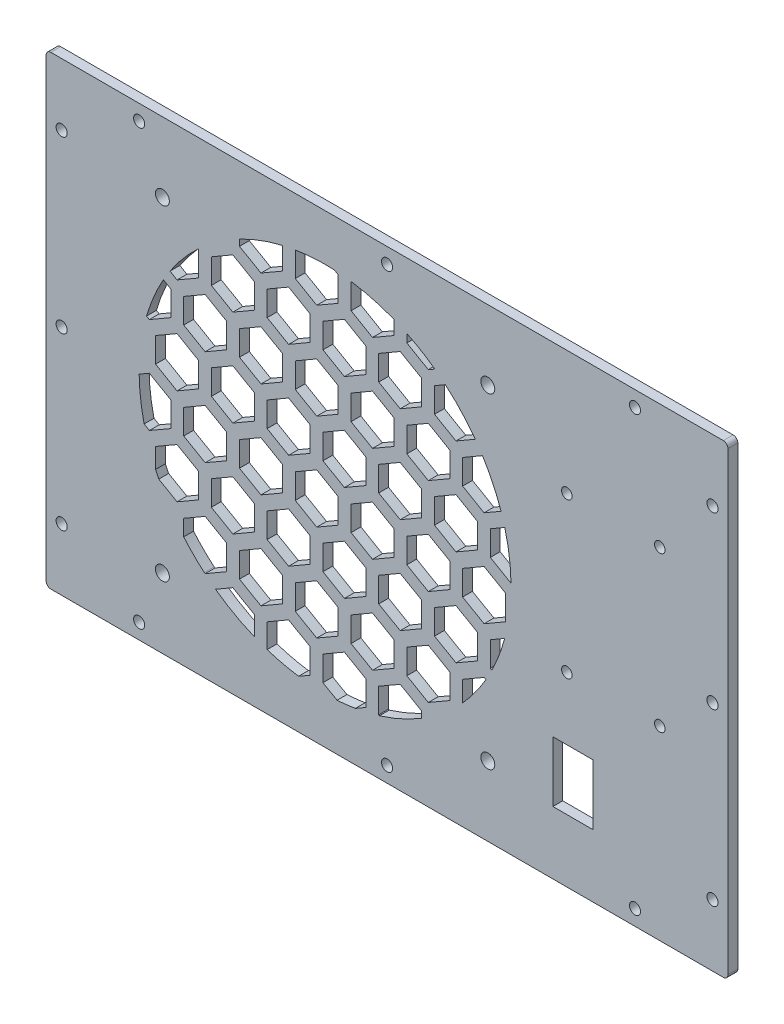
SolidWorks part; units mm, degrees
ref_plane "Front Plane" through (0, 0, 0) normal (0, 0, 1) x (1, 0, 0)
ref_plane "Top Plane" through (0, 0, 0) normal (0, 1, 0) x (1, 0, 0)
ref_plane "Right Plane" through (0, 0, 0) normal (1, 0, 0) x (0, 0, -1)
sketch "Sketch1" plane through (0, 0, 0) normal (0, 0, 1) x (1, 0, 0)
  line L0 (0, 0) -> (0, 75) construction
  line L1 (-110, -75) -> (110, -75)
  line L2 (-110, -75) -> (-110, 75)
  line L3 (-110, 75) -> (110, 75)
  line L4 (110, -75) -> (110, 75)
  line L5 (-110, -75) -> (110, 75) construction
  line L6 (-110, 75) -> (110, -75) construction
  line L15 (0, 0) -> (-110, 0) construction
  point P0 (0, 0)
  dimension "D1" = 220
  dimension "D2" = 150
extrude "Boss-Extrude1" add sketch "Sketch1" along normal blind 3.175 contours L3 L2 L1 L4 region at (0, 0, 0)
hole_wizard "M3 Clearance Hole1" positions "Sketch2" profile "Sketch3" hole size "M3" standard "ANSI Metric" end condition through all
sketch "Sketch2" plane through (0, 0, 3.175) normal (0, 0, 1) x (1, 0, 0)
  line L1 (-105, -70) -> (105, -70)
  line L2 (-105, -70) -> (-105, 70)
  line L3 (-105, 70) -> (105, 70)
  line L4 (105, -70) -> (105, 70)
  line L5 (-105, -70) -> (105, 70) construction
  line L6 (-105, 70) -> (105, -70) construction
  line L7 (-110, -75) -> (-110, 75) construction
  line L8 (-110, 75) -> (110, 75) construction
  point P2 (0, 0)
  point P113 (-80, 70)
  point P115 (80, 70)
  point P116 (0, 70)
  point P118 (-105, 55)
  point P120 (-105, 0)
  point P122 (-105, -55)
  point P124 (-80, -70)
  point P126 (0, -70)
  point P128 (80, -70)
  point P130 (105, -55)
  point P132 (105, 0)
  point P134 (105, 55)
  dimension "D1" = 5
  dimension "D2" = 5
  dimension "D3" = 80
  dimension "D4" = 80
  dimension "D5" = 55
  dimension "D6" = 55
sketch "Sketch3" plane through (0, 0, 3.175) normal (1, 0, 0) x (0, -1, 0)
  line L0 (0, 0) -> (0, 3.175)
  line L1 (0, 3.175) -> (1.8, 3.175)
  line L2 (1.8, 3.175) -> (1.8, 0)
  line L5 (1.8, 0) -> (0, 0)
  line L11 (0, -6.35) -> (0, 107.95) construction
  dimension "Thru Hole Dia." = 3.6
  dimension "Thru Hole Depth" = 3.175
sketch "Sketch4" plane through (0, 0, 3.175) normal (0, 0, 1) x (1, 0, 0)
  line L1 (-5, -5) -> (5, -5)
  line L2 (-5, -5) -> (-5, 5)
  line L3 (-5, 5) -> (5, 5)
  line L4 (5, -5) -> (5, 5)
  line L5 (-5, -5) -> (5, 5) construction
  line L6 (-5, 5) -> (5, -5) construction
  point P0 (0, 0)
  dimension "D1" = 10
  dimension "D2" = 10
extrude "Boss-Extrude2" add sketch "Sketch4" against normal through all
fillet "Fillet2" radius 1.5 4 edges at (-110, -75, 1.5875) (110, -75, 1.5875) (110, 75, 1.5875) (-110, 75, 1.5875)
sketch "Sketch6" plane through (0, 0, 3.175) normal (0, 0, 1) x (1, 0, 0)
  line L0 (-108.5, -75) -> (108.5, -75) construction
  line L1 (-80, -60) -> (40, -60)
  line L2 (-80, -60) -> (-80, 60)
  line L3 (-80, 60) -> (40, 60)
  line L4 (40, -60) -> (40, 60)
  line L5 (-80, -60) -> (40, 60) construction
  line L6 (-80, 60) -> (40, -60) construction
  line L13 (-110, -73.5) -> (-110, 73.5) construction
  line L17 (-72.5, -52.5) -> (32.5, -52.5)
  line L18 (-72.5, -52.5) -> (-72.5, 52.5)
  line L19 (-72.5, 52.5) -> (32.5, 52.5)
  line L20 (32.5, -52.5) -> (32.5, 52.5)
  line L21 (-72.5, -52.5) -> (32.5, 52.5) construction
  line L22 (-72.5, 52.5) -> (32.5, -52.5) construction
  circle A0 centre (-20, 0) radius 60
  point P0 (-20, 0)
  point P5 (-20, 0)
  point P6 (-20, 0)
  dimension "D7" = 120
  dimension "D1" = 120
  dimension "D2" = 120
  dimension "D3" = 15
  dimension "D4" = 30
  dimension "D5" = 105
  dimension "D6" = 105
hole_wizard "M4 Clearance Hole1" positions "Sketch7" profile "Sketch9" hole size "M4" standard "ANSI Metric" end condition through all
sketch "Sketch7" plane through (0, 0, 3.175) normal (0, 0, 1) x (1, 0, 0)
  point P0 (-72.5, 52.5)
  point P3 (32.5, 52.5)
  point P6 (32.5, -52.5)
  point P9 (-72.5, -52.5)
sketch "Sketch9" plane through (-72.5, 52.5, 3.175) normal (1, 0, 0) x (0, -1, 0)
  line L0 (0, 0) -> (0, 3.175)
  line L1 (0, 3.175) -> (2.25, 3.175)
  line L2 (2.25, 3.175) -> (2.25, 0)
  line L5 (2.25, 0) -> (0, 0)
  line L11 (0, -6.35) -> (0, 107.95) construction
  dimension "Thru Hole Dia." = 4.5
  dimension "Thru Hole Depth" = 3.175
extrude "Cut-Extrude1" cut sketch "Sketch6" against normal blind 10 contours L20 A0 L19 L18 L17 | L18 A0 | L19 A0 | A0 L20 | L17 A0 region at (-20, -55.5167, 3.175) region at (-75.5167, 0, 3.175) region at (-20, 0, 3.175) region at (35.5167, 0, 3.175) region at (-20, 55.5167, 3.175)
sketch "Sketch11" plane through (0, 0, 3.175) normal (0, 0, 1) x (1, 0, 0)
  line L0 (-58.6995, -29.7786) -> (-65.6277, -33.7786)
  line L1 (-76.6995, -29.7786) -> (-83.6277, -33.7786)
  line L2 (-83.6277, -33.7786) -> (-83.6277, -41.7786)
  line L3 (-83.6277, -41.7786) -> (-76.6995, -45.7786)
  line L4 (-76.6995, -45.7786) -> (-69.7713, -41.7786)
  line L5 (-69.7713, -41.7786) -> (-69.7713, -33.7786)
  line L6 (-69.7713, -33.7786) -> (-76.6995, -29.7786)
  line L13 (-67.7713, -45.2427) -> (-74.6995, -49.2427)
  line L14 (-74.6995, -49.2427) -> (-74.6995, -57.2427)
  line L15 (-74.6995, -57.2427) -> (-67.7713, -61.2427)
  line L16 (-67.7713, -61.2427) -> (-60.8431, -57.2427)
  line L17 (-60.8431, -57.2427) -> (-60.8431, -49.2427)
  line L18 (-60.8431, -49.2427) -> (-67.7713, -45.2427)
  line L19 (-65.6277, -33.7786) -> (-65.6277, -41.7786)
  line L20 (-65.6277, -41.7786) -> (-58.6995, -45.7786)
  line L21 (-58.6995, -45.7786) -> (-51.7713, -41.7786)
  line L22 (-51.7713, -41.7786) -> (-51.7713, -33.7786)
  line L23 (-51.7713, -33.7786) -> (-58.6995, -29.7786)
  line L24 (-49.7713, -45.2427) -> (-56.6995, -49.2427)
  line L25 (-56.6995, -49.2427) -> (-56.6995, -57.2427)
  line L26 (-56.6995, -57.2427) -> (-49.7713, -61.2427)
  line L27 (-49.7713, -61.2427) -> (-42.8431, -57.2427)
  line L28 (-42.8431, -57.2427) -> (-42.8431, -49.2427)
  line L29 (-42.8431, -49.2427) -> (-49.7713, -45.2427)
  line L30 (-40.6995, -29.7786) -> (-47.6277, -33.7786)
  line L31 (-47.6277, -33.7786) -> (-47.6277, -41.7786)
  line L32 (-47.6277, -41.7786) -> (-40.6995, -45.7786)
  line L33 (-40.6995, -45.7786) -> (-33.7713, -41.7786)
  line L34 (-33.7713, -41.7786) -> (-33.7713, -33.7786)
  line L35 (-33.7713, -33.7786) -> (-40.6995, -29.7786)
  line L36 (-31.7713, -45.2427) -> (-38.6995, -49.2427)
  line L37 (-38.6995, -49.2427) -> (-38.6995, -57.2427)
  line L38 (-38.6995, -57.2427) -> (-31.7713, -61.2427)
  line L39 (-31.7713, -61.2427) -> (-24.8431, -57.2427)
  line L40 (-24.8431, -57.2427) -> (-24.8431, -49.2427)
  line L41 (-24.8431, -49.2427) -> (-31.7713, -45.2427)
  line L42 (-22.6995, -29.7786) -> (-29.6277, -33.7786)
  line L43 (-29.6277, -33.7786) -> (-29.6277, -41.7786)
  line L44 (-29.6277, -41.7786) -> (-22.6995, -45.7786)
  line L45 (-22.6995, -45.7786) -> (-15.7713, -41.7786)
  line L46 (-15.7713, -41.7786) -> (-15.7713, -33.7786)
  line L47 (-15.7713, -33.7786) -> (-22.6995, -29.7786)
  line L48 (-13.7713, -45.2427) -> (-20.6995, -49.2427)
  line L49 (-20.6995, -49.2427) -> (-20.6995, -57.2427)
  line L50 (-20.6995, -57.2427) -> (-13.7713, -61.2427)
  line L51 (-13.7713, -61.2427) -> (-6.8431, -57.2427)
  line L52 (-6.8431, -57.2427) -> (-6.8431, -49.2427)
  line L53 (-6.8431, -49.2427) -> (-13.7713, -45.2427)
  line L54 (-4.6995, -29.7786) -> (-11.6277, -33.7786)
  line L55 (-11.6277, -33.7786) -> (-11.6277, -41.7786)
  line L56 (-11.6277, -41.7786) -> (-4.6995, -45.7786)
  line L57 (-4.6995, -45.7786) -> (2.2287, -41.7786)
  line L58 (2.2287, -41.7786) -> (2.2287, -33.7786)
  line L59 (2.2287, -33.7786) -> (-4.6995, -29.7786)
  line L60 (4.2287, -45.2427) -> (-2.6995, -49.2427)
  line L61 (-2.6995, -49.2427) -> (-2.6995, -57.2427)
  line L62 (-2.6995, -57.2427) -> (4.2287, -61.2427)
  line L63 (4.2287, -61.2427) -> (11.1569, -57.2427)
  line L64 (11.1569, -57.2427) -> (11.1569, -49.2427)
  line L65 (11.1569, -49.2427) -> (4.2287, -45.2427)
  line L66 (13.3005, -29.7786) -> (6.3723, -33.7786)
  line L67 (6.3723, -33.7786) -> (6.3723, -41.7786)
  line L68 (6.3723, -41.7786) -> (13.3005, -45.7786)
  line L69 (13.3005, -45.7786) -> (20.2287, -41.7786)
  line L70 (20.2287, -41.7786) -> (20.2287, -33.7786)
  line L71 (20.2287, -33.7786) -> (13.3005, -29.7786)
  line L72 (22.2287, -45.2427) -> (15.3005, -49.2427)
  line L73 (15.3005, -49.2427) -> (15.3005, -57.2427)
  line L74 (15.3005, -57.2427) -> (22.2287, -61.2427)
  line L75 (22.2287, -61.2427) -> (29.1569, -57.2427)
  line L76 (29.1569, -57.2427) -> (29.1569, -49.2427)
  line L77 (29.1569, -49.2427) -> (22.2287, -45.2427)
  line L78 (31.3005, -29.7786) -> (24.3723, -33.7786)
  line L79 (24.3723, -33.7786) -> (24.3723, -41.7786)
  line L80 (24.3723, -41.7786) -> (31.3005, -45.7786)
  line L81 (31.3005, -45.7786) -> (38.2287, -41.7786)
  line L82 (38.2287, -41.7786) -> (38.2287, -33.7786)
  line L83 (38.2287, -33.7786) -> (31.3005, -29.7786)
  line L84 (40.2287, -45.2427) -> (33.3005, -49.2427)
  line L85 (33.3005, -49.2427) -> (33.3005, -57.2427)
  line L86 (33.3005, -57.2427) -> (40.2287, -61.2427)
  line L87 (40.2287, -61.2427) -> (47.1569, -57.2427)
  line L88 (47.1569, -57.2427) -> (47.1569, -49.2427)
  line L89 (47.1569, -49.2427) -> (40.2287, -45.2427)
  line L90 (-58.6995, 1.2214) -> (-65.6277, -2.7786)
  line L91 (-65.6277, -2.7786) -> (-65.6277, -10.7786)
  line L92 (-65.6277, -10.7786) -> (-58.6995, -14.7786)
  line L93 (-58.6995, -14.7786) -> (-51.7713, -10.7786)
  line L94 (-51.7713, -10.7786) -> (-51.7713, -2.7786)
  line L95 (-51.7713, -2.7786) -> (-58.6995, 1.2214)
  line L96 (-49.7713, -14.2427) -> (-56.6995, -18.2427)
  line L97 (-56.6995, -18.2427) -> (-56.6995, -26.2427)
  line L98 (-56.6995, -26.2427) -> (-49.7713, -30.2427)
  line L99 (-49.7713, -30.2427) -> (-42.8431, -26.2427)
  line L100 (-42.8431, -26.2427) -> (-42.8431, -18.2427)
  line L101 (-42.8431, -18.2427) -> (-49.7713, -14.2427)
  line L102 (-40.6995, 1.2214) -> (-47.6277, -2.7786)
  line L103 (-47.6277, -2.7786) -> (-47.6277, -10.7786)
  line L104 (-47.6277, -10.7786) -> (-40.6995, -14.7786)
  line L105 (-40.6995, -14.7786) -> (-33.7713, -10.7786)
  line L106 (-33.7713, -10.7786) -> (-33.7713, -2.7786)
  line L107 (-33.7713, -2.7786) -> (-40.6995, 1.2214)
  line L108 (-31.7713, -14.2427) -> (-38.6995, -18.2427)
  line L109 (-38.6995, -18.2427) -> (-38.6995, -26.2427)
  line L110 (-38.6995, -26.2427) -> (-31.7713, -30.2427)
  line L111 (-31.7713, -30.2427) -> (-24.8431, -26.2427)
  line L112 (-24.8431, -26.2427) -> (-24.8431, -18.2427)
  line L113 (-24.8431, -18.2427) -> (-31.7713, -14.2427)
  line L114 (-22.6995, 1.2214) -> (-29.6277, -2.7786)
  line L115 (-29.6277, -2.7786) -> (-29.6277, -10.7786)
  line L116 (-29.6277, -10.7786) -> (-22.6995, -14.7786)
  line L117 (-22.6995, -14.7786) -> (-15.7713, -10.7786)
  line L118 (-15.7713, -10.7786) -> (-15.7713, -2.7786)
  line L119 (-15.7713, -2.7786) -> (-22.6995, 1.2214)
  line L120 (-13.7713, -14.2427) -> (-20.6995, -18.2427)
  line L121 (-20.6995, -18.2427) -> (-20.6995, -26.2427)
  line L122 (-20.6995, -26.2427) -> (-13.7713, -30.2427)
  line L123 (-13.7713, -30.2427) -> (-6.8431, -26.2427)
  line L124 (-6.8431, -26.2427) -> (-6.8431, -18.2427)
  line L125 (-6.8431, -18.2427) -> (-13.7713, -14.2427)
  line L126 (-4.6995, 1.2214) -> (-11.6277, -2.7786)
  line L127 (-11.6277, -2.7786) -> (-11.6277, -10.7786)
  line L128 (-11.6277, -10.7786) -> (-4.6995, -14.7786)
  line L129 (-4.6995, -14.7786) -> (2.2287, -10.7786)
  line L130 (2.2287, -10.7786) -> (2.2287, -2.7786)
  line L131 (2.2287, -2.7786) -> (-4.6995, 1.2214)
  line L132 (4.2287, -14.2427) -> (-2.6995, -18.2427)
  line L133 (-2.6995, -18.2427) -> (-2.6995, -26.2427)
  line L134 (-2.6995, -26.2427) -> (4.2287, -30.2427)
  line L135 (4.2287, -30.2427) -> (11.1569, -26.2427)
  line L136 (11.1569, -26.2427) -> (11.1569, -18.2427)
  line L137 (11.1569, -18.2427) -> (4.2287, -14.2427)
  line L138 (13.3005, 1.2214) -> (6.3723, -2.7786)
  line L139 (6.3723, -2.7786) -> (6.3723, -10.7786)
  line L140 (6.3723, -10.7786) -> (13.3005, -14.7786)
  line L141 (13.3005, -14.7786) -> (20.2287, -10.7786)
  line L142 (20.2287, -10.7786) -> (20.2287, -2.7786)
  line L143 (20.2287, -2.7786) -> (13.3005, 1.2214)
  line L144 (22.2287, -14.2427) -> (15.3005, -18.2427)
  line L145 (15.3005, -18.2427) -> (15.3005, -26.2427)
  line L146 (15.3005, -26.2427) -> (22.2287, -30.2427)
  line L147 (22.2287, -30.2427) -> (29.1569, -26.2427)
  line L148 (29.1569, -26.2427) -> (29.1569, -18.2427)
  line L149 (29.1569, -18.2427) -> (22.2287, -14.2427)
  line L150 (31.3005, 1.2214) -> (24.3723, -2.7786)
  line L151 (24.3723, -2.7786) -> (24.3723, -10.7786)
  line L152 (24.3723, -10.7786) -> (31.3005, -14.7786)
  line L153 (31.3005, -14.7786) -> (38.2287, -10.7786)
  line L154 (38.2287, -10.7786) -> (38.2287, -2.7786)
  line L155 (38.2287, -2.7786) -> (31.3005, 1.2214)
  line L156 (40.2287, -14.2427) -> (33.3005, -18.2427)
  line L157 (33.3005, -18.2427) -> (33.3005, -26.2427)
  line L158 (33.3005, -26.2427) -> (40.2287, -30.2427)
  line L159 (40.2287, -30.2427) -> (47.1569, -26.2427)
  line L160 (47.1569, -26.2427) -> (47.1569, -18.2427)
  line L161 (47.1569, -18.2427) -> (40.2287, -14.2427)
  line L162 (-58.6995, 32.2214) -> (-65.6277, 28.2214)
  line L163 (-65.6277, 28.2214) -> (-65.6277, 20.2214)
  line L164 (-65.6277, 20.2214) -> (-58.6995, 16.2214)
  line L165 (-58.6995, 16.2214) -> (-51.7713, 20.2214)
  line L166 (-51.7713, 20.2214) -> (-51.7713, 28.2214)
  line L167 (-51.7713, 28.2214) -> (-58.6995, 32.2214)
  line L168 (-49.7713, 16.7573) -> (-56.6995, 12.7573)
  line L169 (-56.6995, 12.7573) -> (-56.6995, 4.7573)
  line L170 (-56.6995, 4.7573) -> (-49.7713, 0.7573)
  line L171 (-49.7713, 0.7573) -> (-42.8431, 4.7573)
  line L172 (-42.8431, 4.7573) -> (-42.8431, 12.7573)
  line L173 (-42.8431, 12.7573) -> (-49.7713, 16.7573)
  line L174 (-40.6995, 32.2214) -> (-47.6277, 28.2214)
  line L175 (-47.6277, 28.2214) -> (-47.6277, 20.2214)
  line L176 (-47.6277, 20.2214) -> (-40.6995, 16.2214)
  line L177 (-40.6995, 16.2214) -> (-33.7713, 20.2214)
  line L178 (-33.7713, 20.2214) -> (-33.7713, 28.2214)
  line L179 (-33.7713, 28.2214) -> (-40.6995, 32.2214)
  line L180 (-31.7713, 16.7573) -> (-38.6995, 12.7573)
  line L181 (-38.6995, 12.7573) -> (-38.6995, 4.7573)
  line L182 (-38.6995, 4.7573) -> (-31.7713, 0.7573)
  line L183 (-31.7713, 0.7573) -> (-24.8431, 4.7573)
  line L184 (-24.8431, 4.7573) -> (-24.8431, 12.7573)
  line L185 (-24.8431, 12.7573) -> (-31.7713, 16.7573)
  line L186 (-22.6995, 32.2214) -> (-29.6277, 28.2214)
  line L187 (-29.6277, 28.2214) -> (-29.6277, 20.2214)
  line L188 (-29.6277, 20.2214) -> (-22.6995, 16.2214)
  line L189 (-22.6995, 16.2214) -> (-15.7713, 20.2214)
  line L190 (-15.7713, 20.2214) -> (-15.7713, 28.2214)
  line L191 (-15.7713, 28.2214) -> (-22.6995, 32.2214)
  line L192 (-13.7713, 16.7573) -> (-20.6995, 12.7573)
  line L193 (-20.6995, 12.7573) -> (-20.6995, 4.7573)
  line L194 (-20.6995, 4.7573) -> (-13.7713, 0.7573)
  line L195 (-13.7713, 0.7573) -> (-6.8431, 4.7573)
  line L196 (-6.8431, 4.7573) -> (-6.8431, 12.7573)
  line L197 (-6.8431, 12.7573) -> (-13.7713, 16.7573)
  line L198 (-4.6995, 32.2214) -> (-11.6277, 28.2214)
  line L199 (-11.6277, 28.2214) -> (-11.6277, 20.2214)
  line L200 (-11.6277, 20.2214) -> (-4.6995, 16.2214)
  line L201 (-4.6995, 16.2214) -> (2.2287, 20.2214)
  line L202 (2.2287, 20.2214) -> (2.2287, 28.2214)
  line L203 (2.2287, 28.2214) -> (-4.6995, 32.2214)
  line L204 (4.2287, 16.7573) -> (-2.6995, 12.7573)
  line L205 (-2.6995, 12.7573) -> (-2.6995, 4.7573)
  line L206 (-2.6995, 4.7573) -> (4.2287, 0.7573)
  line L207 (4.2287, 0.7573) -> (11.1569, 4.7573)
  line L208 (11.1569, 4.7573) -> (11.1569, 12.7573)
  line L209 (11.1569, 12.7573) -> (4.2287, 16.7573)
  line L210 (13.3005, 32.2214) -> (6.3723, 28.2214)
  line L211 (6.3723, 28.2214) -> (6.3723, 20.2214)
  line L212 (6.3723, 20.2214) -> (13.3005, 16.2214)
  line L213 (13.3005, 16.2214) -> (20.2287, 20.2214)
  line L214 (20.2287, 20.2214) -> (20.2287, 28.2214)
  line L215 (20.2287, 28.2214) -> (13.3005, 32.2214)
  line L216 (22.2287, 16.7573) -> (15.3005, 12.7573)
  line L217 (15.3005, 12.7573) -> (15.3005, 4.7573)
  line L218 (15.3005, 4.7573) -> (22.2287, 0.7573)
  line L219 (22.2287, 0.7573) -> (29.1569, 4.7573)
  line L220 (29.1569, 4.7573) -> (29.1569, 12.7573)
  line L221 (29.1569, 12.7573) -> (22.2287, 16.7573)
  line L222 (31.3005, 32.2214) -> (24.3723, 28.2214)
  line L223 (24.3723, 28.2214) -> (24.3723, 20.2214)
  line L224 (24.3723, 20.2214) -> (31.3005, 16.2214)
  line L225 (31.3005, 16.2214) -> (38.2287, 20.2214)
  line L226 (38.2287, 20.2214) -> (38.2287, 28.2214)
  line L227 (38.2287, 28.2214) -> (31.3005, 32.2214)
  line L228 (40.2287, 16.7573) -> (33.3005, 12.7573)
  line L229 (33.3005, 12.7573) -> (33.3005, 4.7573)
  line L230 (33.3005, 4.7573) -> (40.2287, 0.7573)
  line L231 (40.2287, 0.7573) -> (47.1569, 4.7573)
  line L232 (47.1569, 4.7573) -> (47.1569, 12.7573)
  line L233 (47.1569, 12.7573) -> (40.2287, 16.7573)
  line L234 (-58.6995, 63.2214) -> (-65.6277, 59.2214)
  line L235 (-65.6277, 59.2214) -> (-65.6277, 51.2214)
  line L236 (-65.6277, 51.2214) -> (-58.6995, 47.2214)
  line L237 (-58.6995, 47.2214) -> (-51.7713, 51.2214)
  line L238 (-51.7713, 51.2214) -> (-51.7713, 59.2214)
  line L239 (-51.7713, 59.2214) -> (-58.6995, 63.2214)
  line L240 (-49.7713, 47.7573) -> (-56.6995, 43.7573)
  line L241 (-56.6995, 43.7573) -> (-56.6995, 35.7573)
  line L242 (-56.6995, 35.7573) -> (-49.7713, 31.7573)
  line L243 (-49.7713, 31.7573) -> (-42.8431, 35.7573)
  line L244 (-42.8431, 35.7573) -> (-42.8431, 43.7573)
  line L245 (-42.8431, 43.7573) -> (-49.7713, 47.7573)
  line L246 (-40.6995, 63.2214) -> (-47.6277, 59.2214)
  line L247 (-47.6277, 59.2214) -> (-47.6277, 51.2214)
  line L248 (-47.6277, 51.2214) -> (-40.6995, 47.2214)
  line L249 (-40.6995, 47.2214) -> (-33.7713, 51.2214)
  line L250 (-33.7713, 51.2214) -> (-33.7713, 59.2214)
  line L251 (-33.7713, 59.2214) -> (-40.6995, 63.2214)
  line L252 (-31.7713, 47.7573) -> (-38.6995, 43.7573)
  line L253 (-38.6995, 43.7573) -> (-38.6995, 35.7573)
  line L254 (-38.6995, 35.7573) -> (-31.7713, 31.7573)
  line L255 (-31.7713, 31.7573) -> (-24.8431, 35.7573)
  line L256 (-24.8431, 35.7573) -> (-24.8431, 43.7573)
  line L257 (-24.8431, 43.7573) -> (-31.7713, 47.7573)
  line L258 (-22.6995, 63.2214) -> (-29.6277, 59.2214)
  line L259 (-29.6277, 59.2214) -> (-29.6277, 51.2214)
  line L260 (-29.6277, 51.2214) -> (-22.6995, 47.2214)
  line L261 (-22.6995, 47.2214) -> (-15.7713, 51.2214)
  line L262 (-15.7713, 51.2214) -> (-15.7713, 59.2214)
  line L263 (-15.7713, 59.2214) -> (-22.6995, 63.2214)
  line L264 (-13.7713, 47.7573) -> (-20.6995, 43.7573)
  line L265 (-20.6995, 43.7573) -> (-20.6995, 35.7573)
  line L266 (-20.6995, 35.7573) -> (-13.7713, 31.7573)
  line L267 (-13.7713, 31.7573) -> (-6.8431, 35.7573)
  line L268 (-6.8431, 35.7573) -> (-6.8431, 43.7573)
  line L269 (-6.8431, 43.7573) -> (-13.7713, 47.7573)
  line L270 (-4.6995, 63.2214) -> (-11.6277, 59.2214)
  line L271 (-11.6277, 59.2214) -> (-11.6277, 51.2214)
  line L272 (-11.6277, 51.2214) -> (-4.6995, 47.2214)
  line L273 (-4.6995, 47.2214) -> (2.2287, 51.2214)
  line L274 (2.2287, 51.2214) -> (2.2287, 59.2214)
  line L275 (2.2287, 59.2214) -> (-4.6995, 63.2214)
  line L276 (4.2287, 47.7573) -> (-2.6995, 43.7573)
  line L277 (-2.6995, 43.7573) -> (-2.6995, 35.7573)
  line L278 (-2.6995, 35.7573) -> (4.2287, 31.7573)
  line L279 (4.2287, 31.7573) -> (11.1569, 35.7573)
  line L280 (11.1569, 35.7573) -> (11.1569, 43.7573)
  line L281 (11.1569, 43.7573) -> (4.2287, 47.7573)
  line L282 (13.3005, 63.2214) -> (6.3723, 59.2214)
  line L283 (6.3723, 59.2214) -> (6.3723, 51.2214)
  line L284 (6.3723, 51.2214) -> (13.3005, 47.2214)
  line L285 (13.3005, 47.2214) -> (20.2287, 51.2214)
  line L286 (20.2287, 51.2214) -> (20.2287, 59.2214)
  line L287 (20.2287, 59.2214) -> (13.3005, 63.2214)
  line L288 (22.2287, 47.7573) -> (15.3005, 43.7573)
  line L289 (15.3005, 43.7573) -> (15.3005, 35.7573)
  line L290 (15.3005, 35.7573) -> (22.2287, 31.7573)
  line L291 (22.2287, 31.7573) -> (29.1569, 35.7573)
  line L292 (29.1569, 35.7573) -> (29.1569, 43.7573)
  line L293 (29.1569, 43.7573) -> (22.2287, 47.7573)
  line L294 (31.3005, 63.2214) -> (24.3723, 59.2214)
  line L295 (24.3723, 59.2214) -> (24.3723, 51.2214)
  line L296 (24.3723, 51.2214) -> (31.3005, 47.2214)
  line L297 (31.3005, 47.2214) -> (38.2287, 51.2214)
  line L298 (38.2287, 51.2214) -> (38.2287, 59.2214)
  line L299 (38.2287, 59.2214) -> (31.3005, 63.2214)
  line L300 (40.2287, 47.7573) -> (33.3005, 43.7573)
  line L301 (33.3005, 43.7573) -> (33.3005, 35.7573)
  line L302 (33.3005, 35.7573) -> (40.2287, 31.7573)
  line L303 (40.2287, 31.7573) -> (47.1569, 35.7573)
  line L304 (47.1569, 35.7573) -> (47.1569, 43.7573)
  line L305 (47.1569, 43.7573) -> (40.2287, 47.7573)
  line L306 (-76.6995, 1.2214) -> (-83.6277, -2.7786)
  line L307 (-83.6277, -2.7786) -> (-83.6277, -10.7786)
  line L308 (-83.6277, -10.7786) -> (-76.6995, -14.7786)
  line L309 (-76.6995, -14.7786) -> (-69.7713, -10.7786)
  line L310 (-69.7713, -10.7786) -> (-69.7713, -2.7786)
  line L311 (-69.7713, -2.7786) -> (-76.6995, 1.2214)
  line L312 (-67.7713, -14.2427) -> (-74.6995, -18.2427)
  line L313 (-74.6995, -18.2427) -> (-74.6995, -26.2427)
  line L314 (-74.6995, -26.2427) -> (-67.7713, -30.2427)
  line L315 (-67.7713, -30.2427) -> (-60.8431, -26.2427)
  line L316 (-60.8431, -26.2427) -> (-60.8431, -18.2427)
  line L317 (-60.8431, -18.2427) -> (-67.7713, -14.2427)
  line L318 (-76.6995, 32.2214) -> (-83.6277, 28.2214)
  line L319 (-83.6277, 28.2214) -> (-83.6277, 20.2214)
  line L320 (-83.6277, 20.2214) -> (-76.6995, 16.2214)
  line L321 (-76.6995, 16.2214) -> (-69.7713, 20.2214)
  line L322 (-69.7713, 20.2214) -> (-69.7713, 28.2214)
  line L323 (-69.7713, 28.2214) -> (-76.6995, 32.2214)
  line L324 (-67.7713, 16.7573) -> (-74.6995, 12.7573)
  line L325 (-74.6995, 12.7573) -> (-74.6995, 4.7573)
  line L326 (-74.6995, 4.7573) -> (-67.7713, 0.7573)
  line L327 (-67.7713, 0.7573) -> (-60.8431, 4.7573)
  line L328 (-60.8431, 4.7573) -> (-60.8431, 12.7573)
  line L329 (-60.8431, 12.7573) -> (-67.7713, 16.7573)
  line L330 (-76.6995, 63.2214) -> (-83.6277, 59.2214)
  line L331 (-83.6277, 59.2214) -> (-83.6277, 51.2214)
  line L332 (-83.6277, 51.2214) -> (-76.6995, 47.2214)
  line L333 (-76.6995, 47.2214) -> (-69.7713, 51.2214)
  line L334 (-69.7713, 51.2214) -> (-69.7713, 59.2214)
  line L335 (-69.7713, 59.2214) -> (-76.6995, 63.2214)
  line L336 (-67.7713, 47.7573) -> (-74.6995, 43.7573)
  line L337 (-74.6995, 43.7573) -> (-74.6995, 35.7573)
  line L338 (-74.6995, 35.7573) -> (-67.7713, 31.7573)
  line L339 (-67.7713, 31.7573) -> (-60.8431, 35.7573)
  line L340 (-60.8431, 35.7573) -> (-60.8431, 43.7573)
  line L341 (-60.8431, 43.7573) -> (-67.7713, 47.7573)
  line L346 (-110, 73.5) -> (-110, -73.5)
  line L347 (-108.5, -75) -> (108.5, -75)
  line L348 (110, -73.5) -> (110, 73.5)
  line L349 (108.5, 75) -> (-108.5, 75)
  line L350 (-110, 73.5) -> (-110, -73.5)
  line L351 (-108.5, -75) -> (108.5, -75)
  line L352 (110, -73.5) -> (110, 73.5)
  line L353 (108.5, 75) -> (-108.5, 75)
  circle A0 centre (-76.6995, -37.7786) radius 6.9282 construction
  circle A2 centre (-67.7713, -53.2427) radius 6.9282 construction
  arc A7 (-110, -73.5) -> (-108.5, -75) centre (-108.5, -73.5) ccw
  arc A8 (108.5, -75) -> (110, -73.5) centre (108.5, -73.5) ccw
  arc A9 (110, 73.5) -> (108.5, 75) centre (108.5, 73.5) ccw
  arc A10 (-108.5, 75) -> (-110, 73.5) centre (-108.5, 73.5) ccw
  arc A11 (-110, -73.5) -> (-108.5, -75) centre (-108.5, -73.5) ccw
  arc A12 (108.5, -75) -> (110, -73.5) centre (108.5, -73.5) ccw
  arc A13 (110, 73.5) -> (108.5, 75) centre (108.5, 73.5) ccw
  arc A14 (-108.5, 75) -> (-110, 73.5) centre (-108.5, 73.5) ccw
  circle M347 centre (-20, 0) radius 60
  dimension "D1" = 8
  dimension "D2" = 4
  dimension "D3" = 2
  dimension "D6" = 0
  dimension "D4" = 7
  dimension "D5" = 4
extrude "Boss-Extrude3" add sketch "Sketch11" against normal up to surface (3.175 mm away) contours L341 L340 L339 L338 L323 L322 L321 L320 L306 L311 L310 L309 L308 L313 L312 L317 L316 L315 L314 L19 L0 L23 L22 L21 L20 L24 L29 L28 L37 L36 L41 L40 L39 L50 L49 L48 L53 L52 L51 L62 L61 L60 L65 M347 region at (-20.0079, 0.1732, 3.175) up to face at (40, 0, 0)
sketch "Sketch12" plane through (0, 0, 3.175) normal (0, 0, 1) x (1, 0, 0)
  line L0 (110, -73.5) -> (110, 73.5) construction
  line L1 (53.5, -54.75) -> (66.5, -54.75)
  line L2 (53.5, -54.75) -> (53.5, -35.25)
  line L3 (53.5, -35.25) -> (66.5, -35.25)
  line L4 (66.5, -54.75) -> (66.5, -35.25)
  line L5 (53.5, -54.75) -> (66.5, -35.25) construction
  line L6 (53.5, -35.25) -> (66.5, -54.75) construction
  line L7 (-108.5, -75) -> (108.5, -75) construction
  point P0 (60, -45)
  dimension "D1" = 13
  dimension "D2" = 19.5
  dimension "D3" = 50
  dimension "D4" = 30
extrude "Cut-Extrude2" cut sketch "Sketch12" against normal through all
hole_wizard "M3 Clearance Hole2" positions "Sketch13" profile "Sketch15" hole size "M3" standard "ANSI Metric" end condition through all
sketch "Sketch13" plane through (0, 0, 3.175) normal (0, 0, 1) x (1, 0, 0)
  line L1 (58, 35) -> (88, 35)
  line L2 (58, 35) -> (58, -15)
  line L3 (58, -15) -> (88, -15)
  line L4 (88, 35) -> (88, -15)
  line L5 (110, -73.5) -> (110, 73.5) construction
  line L6 (-108.5, 75) -> (108.5, 75) construction
  point P1 (58, 35)
  point P2 (88, -15)
  point P69 (58, -15)
  point P70 (88, 35)
  point P81 (58.1153, -18.0473)
  dimension "D1" = 30
  dimension "D2" = 50
  dimension "D3" = 22
  dimension "D4" = 40
sketch "Sketch15" plane through (58, 35, 3.175) normal (1, 0, 0) x (0, -1, 0)
  line L0 (0, 0) -> (0, 3.175)
  line L1 (0, 3.175) -> (1.7, 3.175)
  line L2 (1.7, 3.175) -> (1.7, 0)
  line L5 (1.7, 0) -> (0, 0)
  line L11 (0, -6.35) -> (0, 107.95) construction
  dimension "Thru Hole Dia." = 3.4
  dimension "Thru Hole Depth" = 3.175
